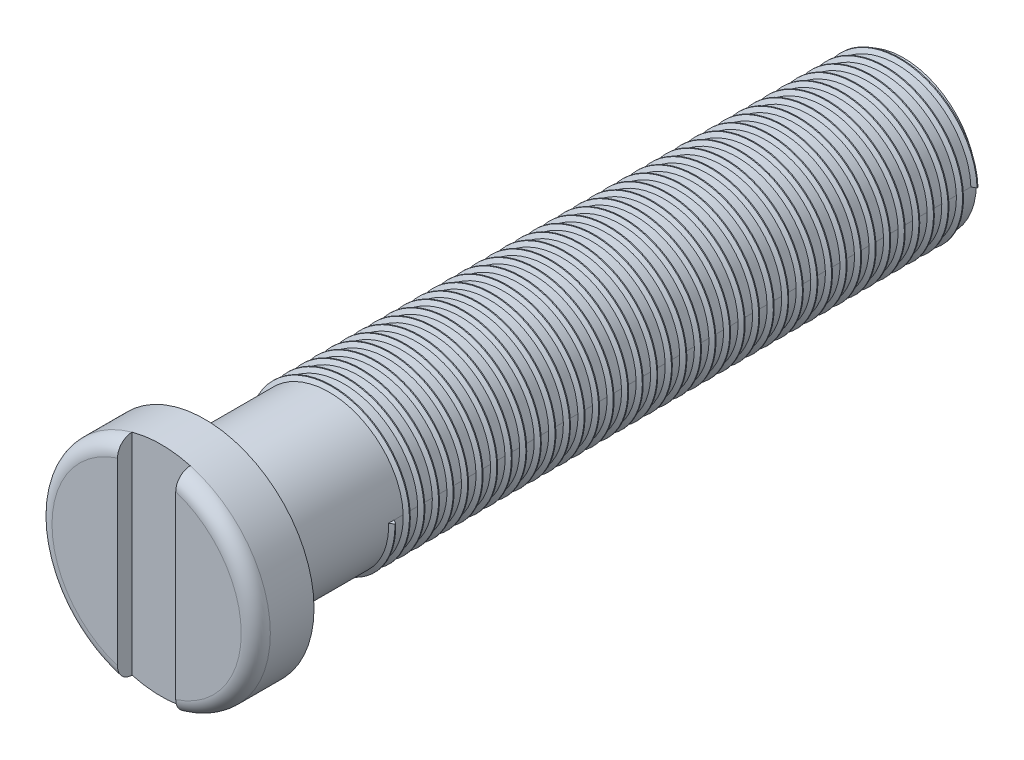
SolidWorks part; units mm, degrees
ref_plane "Front Plane" through (0, 0, 0) normal (0, 0, 1) x (1, 0, 0)
ref_plane "Top Plane" through (0, 0, 0) normal (0, 1, 0) x (1, 0, 0)
ref_plane "Right Plane" through (0, 0, 0) normal (1, 0, 0) x (0, 0, -1)
sketch "Sketch3" plane through (0, 0, 0) normal (0, 0, 1) x (1, 0, 0)
  circle A0 centre (0, 0) radius 2.5
  dimension "D1" = 5
extrude "Boss-Extrude2" add sketch "Sketch3" along normal blind 24
sketch "Sketch4" plane through (0, 0, 24) normal (0, 0, 1) x (1, 0, 0)
  circle A0 centre (0, 0) radius 3.75
  dimension "D1" = 7.5
extrude "Boss-Extrude3" add sketch "Sketch4" along normal blind 2
fillet "Fillet2" radius 0.5 1 edges at (3.75, 0, 26)
sketch "Sketch6" plane through (0, 0, 26) normal (0, 0, 1) x (1, 0, 0)
  line L1 (-1, 3.75) -> (1, 3.75)
  line L2 (-1, 3.75) -> (-1, -3.75)
  line L3 (-1, -3.75) -> (1, -3.75)
  line L4 (1, 3.75) -> (1, -3.75)
  line L5 (-1, 3.75) -> (1, -3.75) construction
  line L6 (-1, -3.75) -> (1, 3.75) construction
  point P0 (0, 0)
  dimension "D1" = 2
  dimension "D2" = 7.5
extrude "Cut-Extrude1" cut sketch "Sketch6" against normal blind 0.5
thread "Thread1" pitch 0.25 method extrude profile "Thread Profile1" start angle 0, offset 0, length 20, pitch 0.5, diameter 5
ref_plane "Plane1" through (2.5, 0, 0) normal (0, -1, 0) x (1, 0, 0)
sketch "Thread Profile1" plane through (2.5, 0, 0) normal (0, -1, 0) x (1, 0, 0)
  line L0 (0, 0) -> (0, 0.25) construction
  line L1 (0, 0) -> (0.1353, 0.0781)
  line L2 (0.1353, 0.0781) -> (0.1353, 0.1094)
  line L3 (0.1353, 0.1094) -> (0, 0.1875)
  line L4 (0.1353, 0.0937) -> (0, 0.0937) construction
  line L11 (0, 0) -> (0, 0.1875)
  point P2 (0, 0)
  dimension "Pitch" = 0.25
  dimension "Profile_Angle" = 60
  dimension "Profile_Land" = 0.0312
  dimension "Profile_Height" = 0.1353
